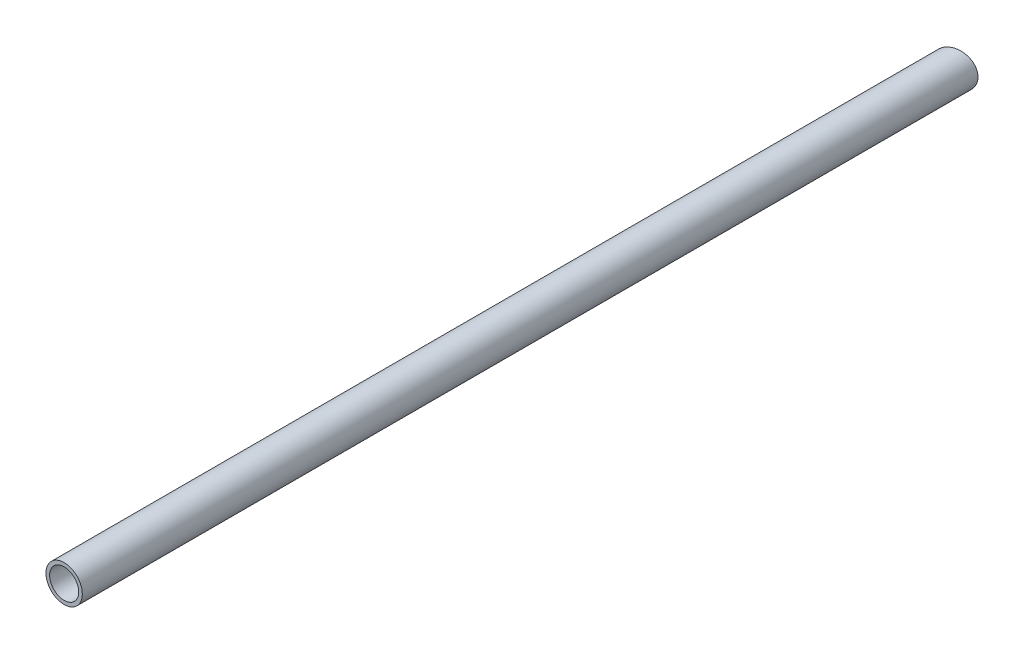
SolidWorks part; units mm, degrees
ref_plane "Front Plane" through (0, 0, 0) normal (0, 0, 1) x (1, 0, 0)
ref_plane "Top Plane" through (0, 0, 0) normal (0, 1, 0) x (1, 0, 0)
ref_plane "Right Plane" through (0, 0, 0) normal (1, 0, 0) x (0, 0, -1)
sketch "Sketch1" plane through (0, 0, 0) normal (0, 0, 1) x (1, 0, 0)
  circle A0 centre (0, 0) radius 15.875
  circle A1 centre (0, 0) radius 12.7
  dimension "D1" = 31.75
  dimension "D2" = 3.175
extrude "Boss-Extrude1" add sketch "Sketch1" along normal blind 782.32
ref_axis "Axis1" through (0, 0, 782.32) along (0, 0, -1)
sketch "Sketch3" plane through (0, 0, 0) normal (0, 1, 0) x (1, 0, 0)
  line L0 (0, 0) -> (15.875, 0)
  line L1 (15.875, 0) -> (-47.625, -17.0148)
  line L2 (15.875, -782.32) -> (15.875, 0) construction
  line L3 (0, 0) -> (-47.625, 0)
  line L4 (-47.625, 0) -> (-47.625, -17.0148)
  dimension "D1" = 15
  dimension "D2" = 63.5
extrude "Cut-Extrude1" cut sketch "Sketch3" against normal through all both and the other way through all
